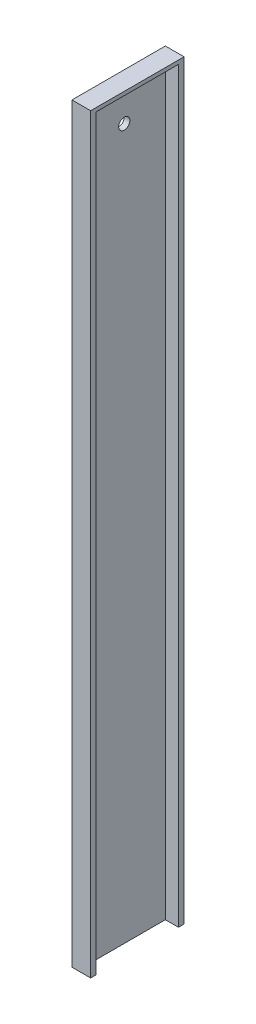
SolidWorks part; units mm, degrees
material "1060 Alloy"
ref_plane "Front Plane" through (0, 0, 0) normal (0, 0, 1) x (1, 0, 0)
ref_plane "Top Plane" through (0, 0, 0) normal (0, 1, 0) x (1, 0, 0)
ref_plane "Right Plane" through (0, 0, 0) normal (1, 0, 0) x (0, 0, -1)
sketch "Sketch1" plane through (0, 0, 0) normal (0, 1, 0) x (1, 0, 0)
  line L0 (-2.5, -12.5) -> (-2.5, 12.5)
  line L1 (-1, -11) -> (1, -11) construction
  line L2 (-1, -11) -> (-1, 11) construction
  line L3 (-1, 11) -> (1, 11) construction
  line L4 (1, -11) -> (1, 11) construction
  line L5 (-1, -11) -> (1, 11) construction
  line L6 (-1, 11) -> (1, -11) construction
  line L7 (-2.5, 12.5) -> (2.5, 12.5)
  line L8 (2.5, -12.5) -> (2.5, 12.5) construction
  line L9 (-2.5, -12.5) -> (2.5, -12.5)
  line L10 (2.5, 11) -> (-1, 11)
  line L11 (-1, 11) -> (-1, -11)
  line L12 (-1, -11) -> (2.5, -11)
  line L13 (2.5, -11) -> (2.5, -12.5)
  line L14 (2.5, 11) -> (2.5, 12.5)
  line L15 (2.5, 11) -> (2.5, -11)
  point P0 (0, 0)
  dimension "D2" = 25
  dimension "D3" = 5
  dimension "D1" = 1.5
extrude "Boss-Extrude1" add sketch "Sketch1" along normal mid plane 200 contours L7 L14 L10 L11 L12 L13 L9 L0
extrude "Boss-Extrude2" add sketch "Sketch1<3>" along normal blind 1 from surface contours L15 L10 L11 L12 | L10 L14 L7 L0 L9 L13 L12 L11 region at (-1.2031, 0, 0) region at (0.75, 0, 0) starting at face at (0.375, 100, 0)
sketch "Sketch1<3>" plane through (0, 0, 0) normal (0, 1, 0) x (1, 0, 0) same geometry as "Sketch1"
sketch "Sketch2" plane through (-1, 0, 0) normal (1, 0, 0) x (0, 0, -1)
  line L0 (12.5, 101) -> (-12.5, 101) construction
  circle A0 centre (0, 90) radius 1.5
  dimension "D1" = 3
  dimension "D2" = 11
extrude "Cut-Extrude1" cut sketch "Sketch2" against normal blind 25
